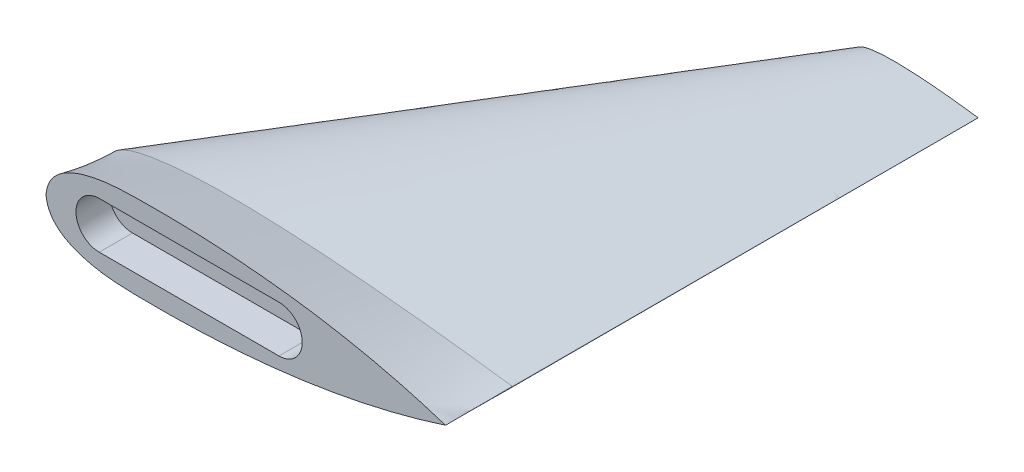
SolidWorks part; units mm, degrees
material "Nylon 101"
ref_plane "Front Plane" through (0, 0, 0) normal (0, 0, 1) x (1, 0, 0)
ref_plane "Top Plane" through (0, 0, 0) normal (0, 1, 0) x (1, 0, 0)
ref_plane "Right Plane" through (0, 0, 0) normal (1, 0, 0) x (0, 0, -1)
curve "Curve1"
  spline degree 3 poles (0.0247, -0.2632, 0) (-0.0121, 0, 0) (0.0247, 0.2632, 0) (0.1356, 0.5197, 0) (0.3168, 0.7666, 0) (0.5661, 1.0049, 0) (0.8827, 1.2355, 0) (1.2661, 1.4585, 0) (1.7158, 1.6738, 0) (2.231, 1.8809, 0) (2.8107, 2.0791, 0) (3.4535, 2.2677, 0) (4.1582, 2.4461, 0) (4.9231, 2.6137, 0) (5.7465, 2.7696, 0) (6.6264, 2.9134, 0) (7.5609, 3.0445, 0) (8.5477, 3.1624, 0) (9.5846, 3.2667, 0) (10.6691, 3.3571, 0) (11.7988, 3.4335, 0) (12.971, 3.4956, 0) (14.1829, 3.5434, 0) (15.4317, 3.5772, 0) (16.7145, 3.597, 0) (18.0284, 3.6032, 0) (19.3702, 3.5962, 0) (20.7368, 3.5763, 0) (22.1251, 3.5442, 0) (23.5317, 3.5004, 0) (24.9534, 3.4457, 0) (26.3869, 3.3806, 0) (27.8289, 3.3059, 0) (29.2759, 3.2225, 0) (30.7246, 3.131, 0) (32.1716, 3.0322, 0) (33.6135, 2.927, 0) (35.047, 2.816, 0) (36.4687, 2.7001, 0) (37.8753, 2.58, 0) (39.2635, 2.4565, 0) (40.6301, 2.3301, 0) (41.9718, 2.2018, 0) (43.2856, 2.072, 0) (44.5683, 1.9415, 0) (45.8171, 1.8109, 0) (47.0288, 1.6809, 0) (48.2009, 1.5521, 0) (49.3304, 1.425, 0) (50.4147, 1.3003, 0) (51.4514, 1.1787, 0) (52.438, 1.0606, 0) (53.3721, 0.9467, 0) (54.2517, 0.8375, 0) (55.0747, 0.7337, 0) (55.839, 0.6357, 0) (56.5431, 0.5442, 0) (57.1851, 0.4596, 0) (57.7637, 0.3825, 0) (58.2774, 0.3132, 0) (58.7251, 0.2523, 0) (59.1055, 0.1998, 0) (59.4184, 0.1573, 0) (59.6615, 0.1216, 0) (59.8381, 0.1013, 0) (59.9395, 0.0794, 0) (60.0436, 0.0813, 0) (60.0436, -0.0813, 0) (59.9395, -0.0794, 0) (59.8381, -0.1013, 0) (59.6615, -0.1216, 0) (59.4184, -0.1573, 0) (59.1055, -0.1998, 0) (58.7251, -0.2523, 0) (58.2774, -0.3132, 0) (57.7637, -0.3825, 0) (57.1851, -0.4596, 0) (56.5431, -0.5442, 0) (55.839, -0.6357, 0) (55.0747, -0.7337, 0) (54.2517, -0.8375, 0) (53.3721, -0.9467, 0) (52.438, -1.0606, 0) (51.4514, -1.1787, 0) (50.4147, -1.3003, 0) (49.3304, -1.425, 0) (48.2009, -1.5521, 0) (47.0288, -1.6809, 0) (45.8171, -1.8109, 0) (44.5683, -1.9415, 0) (43.2856, -2.072, 0) (41.9718, -2.2018, 0) (40.6301, -2.3301, 0) (39.2635, -2.4565, 0) (37.8753, -2.58, 0) (36.4687, -2.7001, 0) (35.047, -2.816, 0) (33.6135, -2.927, 0) (32.1716, -3.0322, 0) (30.7246, -3.131, 0) (29.2759, -3.2225, 0) (27.8289, -3.3059, 0) (26.3869, -3.3806, 0) (24.9534, -3.4457, 0) (23.5317, -3.5004, 0) (22.1251, -3.5442, 0) (20.7368, -3.5763, 0) (19.3702, -3.5962, 0) (18.0284, -3.6032, 0) (16.7145, -3.597, 0) (15.4317, -3.5772, 0) (14.1829, -3.5434, 0) (12.971, -3.4956, 0) (11.7988, -3.4335, 0) (10.6691, -3.3571, 0) (9.5846, -3.2667, 0) (8.5477, -3.1624, 0) (7.5609, -3.0445, 0) (6.6264, -2.9134, 0) (5.7465, -2.7696, 0) (4.9231, -2.6137, 0) (4.1582, -2.4461, 0) (3.4535, -2.2677, 0) (2.8107, -2.0791, 0) (2.231, -1.8809, 0) (1.7158, -1.6738, 0) (1.2661, -1.4585, 0) (0.8827, -1.2355, 0) (0.5661, -1.0049, 0) (0.3168, -0.7666, 0) (0.1356, -0.5197, 0) (0.0247, -0.2632, 0) (-0.0121, 0, 0) (0.0247, 0.2632, 0) knots -0.006773 -0.004321 -0.002106 0 0.002106 0.004321 0.006773 0.009557 0.012734 0.016343 0.020406 0.024934 0.029933 0.035402 0.041337 0.047732 0.054575 0.061857 0.069565 0.077682 0.086195 0.095084 0.104333 0.113922 0.123829 0.134035 0.144516 0.155249 0.16621 0.177376 0.18872 0.200217 0.21184 0.223563 0.235359 0.2472 0.259058 0.270907 0.282718 0.294465 0.306118 0.317651 0.329037 0.340249 0.35126 0.362045 0.372579 0.382836 0.392793 0.402425 0.411711 0.420628 0.429156 0.437273 0.444962 0.452203 0.458979 0.465275 0.471075 0.476366 0.481134 0.485369 0.48906 0.492198 0.494776 0.496788 0.498228 0.499094 0.499383 0.500617 0.500906 0.501772 0.503212 0.505224 0.507802 0.51094 0.514631 0.518866 0.523634 0.528925 0.534725 0.541021 0.547797 0.555038 0.562727 0.570844 0.579372 0.588289 0.597575 0.607207 0.617164 0.627421 0.637955 0.64874 0.659751 0.670963 0.682349 0.693882 0.705535 0.717282 0.729093 0.740942 0.7528 0.764641 0.776437 0.78816 0.799783 0.81128 0.822624 0.83379 0.844751 0.855484 0.865965 0.876171 0.886078 0.895667 0.904916 0.913805 0.922318 0.930435 0.938143 0.945425 0.952268 0.958663 0.964598 0.970067 0.975066 0.979594 0.983657 0.987266 0.990443 0.993227 0.995679 0.997894 1 1.002106 1.004321 1.006773 periodic
sketch "Sketch2" plane through (0, 0, 0) normal (0, 0, 1) x (1, 0, 0)
  spline S0 degree 3 poles (0.0247, 0.2632) (-0.0121, 0) (0.0247, -0.2632) (0.1356, -0.5197) (0.3168, -0.7666) (0.5661, -1.0049) (0.8827, -1.2355) (1.2661, -1.4585) (1.7158, -1.6738) (2.231, -1.8809) (2.8107, -2.0791) (3.4535, -2.2677) (4.1582, -2.4461) (4.9231, -2.6137) (5.7465, -2.7696) (6.6264, -2.9134) (7.5609, -3.0445) (8.5477, -3.1624) (9.5846, -3.2667) (10.6691, -3.3571) (11.7988, -3.4335) (12.971, -3.4956) (14.1829, -3.5434) (15.4317, -3.5772) (16.7145, -3.597) (18.0284, -3.6032) (19.3702, -3.5962) (20.7368, -3.5763) (22.1251, -3.5442) (23.5317, -3.5004) (24.9534, -3.4457) (26.3869, -3.3806) (27.8289, -3.3059) (29.2759, -3.2225) (30.7246, -3.131) (32.1716, -3.0322) (33.6135, -2.927) (35.047, -2.816) (36.4687, -2.7001) (37.8753, -2.58) (39.2635, -2.4565) (40.6301, -2.3301) (41.9718, -2.2018) (43.2856, -2.072) (44.5683, -1.9415) (45.8171, -1.8109) (47.0288, -1.6809) (48.2009, -1.5521) (49.3304, -1.425) (50.4147, -1.3003) (51.4514, -1.1787) (52.438, -1.0606) (53.3721, -0.9467) (54.2517, -0.8375) (55.0747, -0.7337) (55.839, -0.6357) (56.5431, -0.5442) (57.1851, -0.4596) (57.7637, -0.3825) (58.2774, -0.3132) (58.7251, -0.2523) (59.1055, -0.1998) (59.4184, -0.1573) (59.6615, -0.1216) (59.8381, -0.1013) (59.9395, -0.0794) (60.0436, -0.0813) (60.0436, 0.0813) (59.9395, 0.0794) (59.8381, 0.1013) (59.6615, 0.1216) (59.4184, 0.1573) (59.1055, 0.1998) (58.7251, 0.2523) (58.2774, 0.3132) (57.7637, 0.3825) (57.1851, 0.4596) (56.5431, 0.5442) (55.839, 0.6357) (55.0747, 0.7337) (54.2517, 0.8375) (53.3721, 0.9467) (52.438, 1.0606) (51.4514, 1.1787) (50.4147, 1.3003) (49.3304, 1.425) (48.2009, 1.5521) (47.0288, 1.6809) (45.8171, 1.8109) (44.5683, 1.9415) (43.2856, 2.072) (41.9718, 2.2018) (40.6301, 2.3301) (39.2635, 2.4565) (37.8753, 2.58) (36.4687, 2.7001) (35.047, 2.816) (33.6135, 2.927) (32.1716, 3.0322) (30.7246, 3.131) (29.2759, 3.2225) (27.8289, 3.3059) (26.3869, 3.3806) (24.9534, 3.4457) (23.5317, 3.5004) (22.1251, 3.5442) (20.7368, 3.5763) (19.3702, 3.5962) (18.0284, 3.6032) (16.7145, 3.597) (15.4317, 3.5772) (14.1829, 3.5434) (12.971, 3.4956) (11.7988, 3.4335) (10.6691, 3.3571) (9.5846, 3.2667) (8.5477, 3.1624) (7.5609, 3.0445) (6.6264, 2.9134) (5.7465, 2.7696) (4.9231, 2.6137) (4.1582, 2.4461) (3.4535, 2.2677) (2.8107, 2.0791) (2.231, 1.8809) (1.7158, 1.6738) (1.2661, 1.4585) (0.8827, 1.2355) (0.5661, 1.0049) (0.3168, 0.7666) (0.1356, 0.5197) (0.0247, 0.2632) (-0.0121, 0) (0.0247, -0.2632) knots -0.006773 -0.004321 -0.002106 0 0.002106 0.004321 0.006773 0.009557 0.012734 0.016343 0.020406 0.024934 0.029933 0.035402 0.041337 0.047732 0.054575 0.061857 0.069565 0.077682 0.086195 0.095084 0.104333 0.113922 0.123829 0.134035 0.144516 0.155249 0.16621 0.177376 0.18872 0.200217 0.21184 0.223563 0.235359 0.2472 0.259058 0.270907 0.282718 0.294465 0.306118 0.317651 0.329037 0.340249 0.35126 0.362045 0.372579 0.382836 0.392793 0.402425 0.411711 0.420628 0.429156 0.437273 0.444962 0.452203 0.458979 0.465275 0.471075 0.476366 0.481134 0.485369 0.48906 0.492198 0.494776 0.496788 0.498228 0.499094 0.499383 0.500617 0.500906 0.501772 0.503212 0.505224 0.507802 0.51094 0.514631 0.518866 0.523634 0.528925 0.534725 0.541021 0.547797 0.555038 0.562727 0.570844 0.579372 0.588289 0.597575 0.607207 0.617164 0.627421 0.637955 0.64874 0.659751 0.670963 0.682349 0.693882 0.705535 0.717282 0.729093 0.740942 0.7528 0.764641 0.776437 0.78816 0.799783 0.81128 0.822624 0.83379 0.844751 0.855484 0.865965 0.876171 0.886078 0.895667 0.904916 0.913805 0.922318 0.930435 0.938143 0.945425 0.952268 0.958663 0.964598 0.970067 0.975066 0.979594 0.983657 0.987266 0.990443 0.993227 0.995679 0.997894 1 1.002106 1.004321 1.006773 only from (0, 0) to (0, 0) construction
  spline S1 degree 3 poles (0.0247, 0.2632) (-0.0121, 0) (0.0247, -0.2632) (0.1356, -0.5197) (0.3168, -0.7666) (0.5661, -1.0049) (0.8827, -1.2355) (1.2661, -1.4585) (1.7158, -1.6738) (2.231, -1.8809) (2.8107, -2.0791) (3.4535, -2.2677) (4.1582, -2.4461) (4.9231, -2.6137) (5.7465, -2.7696) (6.6264, -2.9134) (7.5609, -3.0445) (8.5477, -3.1624) (9.5846, -3.2667) (10.6691, -3.3571) (11.7988, -3.4335) (12.971, -3.4956) (14.1829, -3.5434) (15.4317, -3.5772) (16.7145, -3.597) (18.0284, -3.6032) (19.3702, -3.5962) (20.7368, -3.5763) (22.1251, -3.5442) (23.5317, -3.5004) (24.9534, -3.4457) (26.3869, -3.3806) (27.8289, -3.3059) (29.2759, -3.2225) (30.7246, -3.131) (32.1716, -3.0322) (33.6135, -2.927) (35.047, -2.816) (36.4687, -2.7001) (37.8753, -2.58) (39.2635, -2.4565) (40.6301, -2.3301) (41.9718, -2.2018) (43.2856, -2.072) (44.5683, -1.9415) (45.8171, -1.8109) (47.0288, -1.6809) (48.2009, -1.5521) (49.3304, -1.425) (50.4147, -1.3003) (51.4514, -1.1787) (52.438, -1.0606) (53.3721, -0.9467) (54.2517, -0.8375) (55.0747, -0.7337) (55.839, -0.6357) (56.5431, -0.5442) (57.1851, -0.4596) (57.7637, -0.3825) (58.2774, -0.3132) (58.7251, -0.2523) (59.1055, -0.1998) (59.4184, -0.1573) (59.6615, -0.1216) (59.8381, -0.1013) (59.9395, -0.0794) (60.0436, -0.0813) (60.0436, 0.0813) (59.9395, 0.0794) (59.8381, 0.1013) (59.6615, 0.1216) (59.4184, 0.1573) (59.1055, 0.1998) (58.7251, 0.2523) (58.2774, 0.3132) (57.7637, 0.3825) (57.1851, 0.4596) (56.5431, 0.5442) (55.839, 0.6357) (55.0747, 0.7337) (54.2517, 0.8375) (53.3721, 0.9467) (52.438, 1.0606) (51.4514, 1.1787) (50.4147, 1.3003) (49.3304, 1.425) (48.2009, 1.5521) (47.0288, 1.6809) (45.8171, 1.8109) (44.5683, 1.9415) (43.2856, 2.072) (41.9718, 2.2018) (40.6301, 2.3301) (39.2635, 2.4565) (37.8753, 2.58) (36.4687, 2.7001) (35.047, 2.816) (33.6135, 2.927) (32.1716, 3.0322) (30.7246, 3.131) (29.2759, 3.2225) (27.8289, 3.3059) (26.3869, 3.3806) (24.9534, 3.4457) (23.5317, 3.5004) (22.1251, 3.5442) (20.7368, 3.5763) (19.3702, 3.5962) (18.0284, 3.6032) (16.7145, 3.597) (15.4317, 3.5772) (14.1829, 3.5434) (12.971, 3.4956) (11.7988, 3.4335) (10.6691, 3.3571) (9.5846, 3.2667) (8.5477, 3.1624) (7.5609, 3.0445) (6.6264, 2.9134) (5.7465, 2.7696) (4.9231, 2.6137) (4.1582, 2.4461) (3.4535, 2.2677) (2.8107, 2.0791) (2.231, 1.8809) (1.7158, 1.6738) (1.2661, 1.4585) (0.8827, 1.2355) (0.5661, 1.0049) (0.3168, 0.7666) (0.1356, 0.5197) (0.0247, 0.2632) (-0.0121, 0) (0.0247, -0.2632) knots -0.006773 -0.004321 -0.002106 0 0.002106 0.004321 0.006773 0.009557 0.012734 0.016343 0.020406 0.024934 0.029933 0.035402 0.041337 0.047732 0.054575 0.061857 0.069565 0.077682 0.086195 0.095084 0.104333 0.113922 0.123829 0.134035 0.144516 0.155249 0.16621 0.177376 0.18872 0.200217 0.21184 0.223563 0.235359 0.2472 0.259058 0.270907 0.282718 0.294465 0.306118 0.317651 0.329037 0.340249 0.35126 0.362045 0.372579 0.382836 0.392793 0.402425 0.411711 0.420628 0.429156 0.437273 0.444962 0.452203 0.458979 0.465275 0.471075 0.476366 0.481134 0.485369 0.48906 0.492198 0.494776 0.496788 0.498228 0.499094 0.499383 0.500617 0.500906 0.501772 0.503212 0.505224 0.507802 0.51094 0.514631 0.518866 0.523634 0.528925 0.534725 0.541021 0.547797 0.555038 0.562727 0.570844 0.579372 0.588289 0.597575 0.607207 0.617164 0.627421 0.637955 0.64874 0.659751 0.670963 0.682349 0.693882 0.705535 0.717282 0.729093 0.740942 0.7528 0.764641 0.776437 0.78816 0.799783 0.81128 0.822624 0.83379 0.844751 0.855484 0.865965 0.876171 0.886078 0.895667 0.904916 0.913805 0.922318 0.930435 0.938143 0.945425 0.952268 0.958663 0.964598 0.970067 0.975066 0.979594 0.983657 0.987266 0.990443 0.993227 0.995679 0.997894 1 1.002106 1.004321 1.006773 only from (0, 0) to (0, 0)
ref_plane "Plane1" through (0, 0, 70) normal (0, 0, 1) x (1, 0, 0)
sketch "Sketch3" plane through (0, 0, 70) normal (0, 0, 1) x (1, 0, 0)
  spline S1 degree 3 poles (42.0303, 0.079) (42.0193, 0) (42.0303, -0.079) (42.0636, -0.1559) (42.1179, -0.23) (42.1927, -0.3015) (42.2877, -0.3706) (42.4027, -0.4376) (42.5376, -0.5021) (42.6922, -0.5643) (42.8661, -0.6237) (43.0589, -0.6803) (43.2703, -0.7338) (43.4998, -0.7841) (43.7468, -0.8309) (44.0108, -0.874) (44.2911, -0.9134) (44.5872, -0.9487) (44.8983, -0.98) (45.2236, -1.0071) (45.5625, -1.03) (45.9142, -1.0487) (46.2777, -1.063) (46.6524, -1.0732) (47.0372, -1.0791) (47.4314, -1.081) (47.8339, -1.0789) (48.2439, -1.0729) (48.6604, -1.0633) (49.0824, -1.0501) (49.5089, -1.0337) (49.939, -1.0142) (50.3715, -0.9918) (50.8056, -0.9667) (51.2403, -0.9393) (51.6744, -0.9097) (52.1069, -0.8781) (52.537, -0.8448) (52.9635, -0.81) (53.3855, -0.774) (53.8019, -0.7369) (54.2119, -0.699) (54.6144, -0.6605) (55.0086, -0.6216) (55.3934, -0.5825) (55.768, -0.5433) (56.1315, -0.5043) (56.4831, -0.4656) (56.822, -0.4275) (57.1473, -0.3901) (57.4583, -0.3536) (57.7543, -0.3182) (58.0345, -0.284) (58.2984, -0.2513) (58.5453, -0.2201) (58.7746, -0.1907) (58.9858, -0.1633) (59.1784, -0.1379) (59.352, -0.1147) (59.5061, -0.094) (59.6404, -0.0757) (59.7545, -0.0599) (59.8484, -0.0472) (59.9213, -0.0365) (59.9743, -0.0304) (60.0047, -0.0238) (60.0359, -0.0244) (60.0359, 0.0244) (60.0047, 0.0238) (59.9743, 0.0304) (59.9213, 0.0365) (59.8484, 0.0472) (59.7545, 0.0599) (59.6404, 0.0757) (59.5061, 0.094) (59.352, 0.1147) (59.1784, 0.1379) (58.9858, 0.1633) (58.7746, 0.1907) (58.5453, 0.2201) (58.2984, 0.2513) (58.0345, 0.284) (57.7543, 0.3182) (57.4583, 0.3536) (57.1473, 0.3901) (56.822, 0.4275) (56.4831, 0.4656) (56.1315, 0.5043) (55.768, 0.5433) (55.3934, 0.5825) (55.0086, 0.6216) (54.6144, 0.6605) (54.2119, 0.699) (53.8019, 0.7369) (53.3855, 0.774) (52.9635, 0.81) (52.537, 0.8448) (52.1069, 0.8781) (51.6744, 0.9097) (51.2403, 0.9393) (50.8056, 0.9667) (50.3715, 0.9918) (49.939, 1.0142) (49.5089, 1.0337) (49.0824, 1.0501) (48.6604, 1.0633) (48.2439, 1.0729) (47.8339, 1.0789) (47.4314, 1.081) (47.0372, 1.0791) (46.6524, 1.0732) (46.2777, 1.063) (45.9142, 1.0487) (45.5625, 1.03) (45.2236, 1.0071) (44.8983, 0.98) (44.5872, 0.9487) (44.2911, 0.9134) (44.0108, 0.874) (43.7468, 0.8309) (43.4998, 0.7841) (43.2703, 0.7338) (43.0589, 0.6803) (42.8661, 0.6237) (42.6922, 0.5643) (42.5376, 0.5021) (42.4027, 0.4376) (42.2877, 0.3706) (42.1927, 0.3015) (42.1179, 0.23) (42.0636, 0.1559) (42.0303, 0.079) (42.0193, 0) (42.0303, -0.079) knots -0.006773 -0.004321 -0.002106 0 0.002106 0.004321 0.006773 0.009557 0.012734 0.016343 0.020406 0.024934 0.029933 0.035402 0.041337 0.047732 0.054575 0.061857 0.069565 0.077682 0.086195 0.095084 0.104333 0.113922 0.123829 0.134035 0.144516 0.155249 0.16621 0.177376 0.18872 0.200217 0.21184 0.223563 0.235359 0.2472 0.259058 0.270907 0.282718 0.294465 0.306118 0.317651 0.329037 0.340249 0.35126 0.362045 0.372579 0.382836 0.392793 0.402425 0.411711 0.420628 0.429156 0.437273 0.444962 0.452203 0.458979 0.465275 0.471075 0.476366 0.481134 0.485369 0.48906 0.492198 0.494776 0.496788 0.498228 0.499094 0.499383 0.500617 0.500906 0.501772 0.503212 0.505224 0.507802 0.51094 0.514631 0.518866 0.523634 0.528925 0.534725 0.541021 0.547797 0.555038 0.562727 0.570844 0.579372 0.588289 0.597575 0.607207 0.617164 0.627421 0.637955 0.64874 0.659751 0.670963 0.682349 0.693882 0.705535 0.717282 0.729093 0.740942 0.7528 0.764641 0.776437 0.78816 0.799783 0.81128 0.822624 0.83379 0.844751 0.855484 0.865965 0.876171 0.886078 0.895667 0.904916 0.913805 0.922318 0.930435 0.938143 0.945425 0.952268 0.958663 0.964598 0.970067 0.975066 0.979594 0.983657 0.987266 0.990443 0.993227 0.995679 0.997894 1 1.002106 1.004321 1.006773 only from (42.0229, 0) to (42.0229, 0)
loft "Loft1" add profiles "Sketch3", "Sketch2" connector at (42.0229, 0, 70) connector at (0, 0, 0)
ref_plane "Plane2" through (0, 0, -10) normal (0, 0, -1) x (-1, 0, 0)
sketch "Sketch8" plane through (0, 0, -10) normal (0, 0, -1) x (-1, 0, 0)
  line L0 (-60.0327, 0) -> (0, 0) construction
  spline S0 degree 3 poles (-60.0327, 0) (-45.2292, 4.8224) (-26.6873, 6.8711) (-5.795, 6.0929) (-0.2693, 3.2539) (0, 0) knots 0 0 0 0 0.739004 0.864029 1 1 1 1
  spline S1 degree 3 poles (-0.0247, -0.2632) (0.0121, 0) (-0.0247, 0.2632) (-0.1356, 0.5197) (-0.3168, 0.7666) (-0.5661, 1.0049) (-0.8827, 1.2355) (-1.2661, 1.4585) (-1.7158, 1.6738) (-2.231, 1.8809) (-2.8107, 2.0791) (-3.4535, 2.2677) (-4.1582, 2.4461) (-4.9231, 2.6137) (-5.7465, 2.7696) (-6.6264, 2.9134) (-7.5609, 3.0445) (-8.5477, 3.1624) (-9.5846, 3.2667) (-10.6691, 3.3571) (-11.7988, 3.4335) (-12.971, 3.4956) (-14.1829, 3.5434) (-15.4317, 3.5772) (-16.7145, 3.597) (-18.0284, 3.6032) (-19.3702, 3.5962) (-20.7368, 3.5763) (-22.1251, 3.5442) (-23.5317, 3.5004) (-24.9534, 3.4457) (-26.3869, 3.3806) (-27.8289, 3.3059) (-29.2759, 3.2225) (-30.7246, 3.131) (-32.1716, 3.0322) (-33.6135, 2.927) (-35.047, 2.816) (-36.4687, 2.7001) (-37.8753, 2.58) (-39.2635, 2.4565) (-40.6301, 2.3301) (-41.9718, 2.2018) (-43.2856, 2.072) (-44.5683, 1.9415) (-45.8171, 1.8109) (-47.0288, 1.6809) (-48.2009, 1.5521) (-49.3304, 1.425) (-50.4147, 1.3003) (-51.4514, 1.1787) (-52.438, 1.0606) (-53.3721, 0.9467) (-54.2517, 0.8375) (-55.0747, 0.7337) (-55.839, 0.6357) (-56.5431, 0.5442) (-57.1851, 0.4596) (-57.7637, 0.3825) (-58.2774, 0.3132) (-58.7251, 0.2523) (-59.1055, 0.1998) (-59.4184, 0.1573) (-59.6615, 0.1216) (-59.8381, 0.1013) (-59.9395, 0.0794) (-60.0436, 0.0813) (-60.0436, -0.0813) (-59.9395, -0.0794) (-59.8381, -0.1013) (-59.6615, -0.1216) (-59.4184, -0.1573) (-59.1055, -0.1998) (-58.7251, -0.2523) (-58.2774, -0.3132) (-57.7637, -0.3825) (-57.1851, -0.4596) (-56.5431, -0.5442) (-55.839, -0.6357) (-55.0747, -0.7337) (-54.2517, -0.8375) (-53.3721, -0.9467) (-52.438, -1.0606) (-51.4514, -1.1787) (-50.4147, -1.3003) (-49.3304, -1.425) (-48.2009, -1.5521) (-47.0288, -1.6809) (-45.8171, -1.8109) (-44.5683, -1.9415) (-43.2856, -2.072) (-41.9718, -2.2018) (-40.6301, -2.3301) (-39.2635, -2.4565) (-37.8753, -2.58) (-36.4687, -2.7001) (-35.047, -2.816) (-33.6135, -2.927) (-32.1716, -3.0322) (-30.7246, -3.131) (-29.2759, -3.2225) (-27.8289, -3.3059) (-26.3869, -3.3806) (-24.9534, -3.4457) (-23.5317, -3.5004) (-22.1251, -3.5442) (-20.7368, -3.5763) (-19.3702, -3.5962) (-18.0284, -3.6032) (-16.7145, -3.597) (-15.4317, -3.5772) (-14.1829, -3.5434) (-12.971, -3.4956) (-11.7988, -3.4335) (-10.6691, -3.3571) (-9.5846, -3.2667) (-8.5477, -3.1624) (-7.5609, -3.0445) (-6.6264, -2.9134) (-5.7465, -2.7696) (-4.9231, -2.6137) (-4.1582, -2.4461) (-3.4535, -2.2677) (-2.8107, -2.0791) (-2.231, -1.8809) (-1.7158, -1.6738) (-1.2661, -1.4585) (-0.8827, -1.2355) (-0.5661, -1.0049) (-0.3168, -0.7666) (-0.1356, -0.5197) (-0.0247, -0.2632) (0.0121, 0) (-0.0247, 0.2632) knots -0.006773 -0.004321 -0.002106 0 0.002106 0.004321 0.006773 0.009557 0.012734 0.016343 0.020406 0.024934 0.029933 0.035402 0.041337 0.047732 0.054575 0.061857 0.069565 0.077682 0.086195 0.095084 0.104333 0.113922 0.123829 0.134035 0.144516 0.155249 0.16621 0.177376 0.18872 0.200217 0.21184 0.223563 0.235359 0.2472 0.259058 0.270907 0.282718 0.294465 0.306118 0.317651 0.329037 0.340249 0.35126 0.362045 0.372579 0.382836 0.392793 0.402425 0.411711 0.420628 0.429156 0.437273 0.444962 0.452203 0.458979 0.465275 0.471075 0.476366 0.481134 0.485369 0.48906 0.492198 0.494776 0.496788 0.498228 0.499094 0.499383 0.500617 0.500906 0.501772 0.503212 0.505224 0.507802 0.51094 0.514631 0.518866 0.523634 0.528925 0.534725 0.541021 0.547797 0.555038 0.562727 0.570844 0.579372 0.588289 0.597575 0.607207 0.617164 0.627421 0.637955 0.64874 0.659751 0.670963 0.682349 0.693882 0.705535 0.717282 0.729093 0.740942 0.7528 0.764641 0.776437 0.78816 0.799783 0.81128 0.822624 0.83379 0.844751 0.855484 0.865965 0.876171 0.886078 0.895667 0.904916 0.913805 0.922318 0.930435 0.938143 0.945425 0.952268 0.958663 0.964598 0.970067 0.975066 0.979594 0.983657 0.987266 0.990443 0.993227 0.995679 0.997894 1 1.002106 1.004321 1.006773 only from (0, 0) to (0, 0) construction
  spline S2 degree 3 poles (-60.0327, 0) (-45.2292, -4.8224) (-26.6873, -6.8711) (-5.795, -6.0929) (-0.2693, -3.2539) (0, 0) knots 0 0 0 0 0.739004 0.864029 1 1 1 1
loft "Loft2" add profiles "Sketch8", "Sketch2<3>" connector at (0, 0, -10) connector at (60.019, 0.0575, 0)
sketch "Sketch2<3>" plane through (0, 0, 0) normal (0, 0, 1) x (1, 0, 0) same geometry as "Sketch2"
sketch "Sketch9" plane through (0, 0, -10) normal (0, 0, -1) x (-1, 0, 0)
  line L0 (-35, 0) -> (-8, 0) construction
  line L1 (-35, 3.5) -> (-8, 3.5)
  line L2 (-35, -3.5) -> (-8, -3.5)
  arc A0 (-35, 3.5) -> (-35, -3.5) centre (-35, 0) ccw
  arc A1 (-8, -3.5) -> (-8, 3.5) centre (-8, 0) ccw
  point P3 (-21.5, 0)
  point P8 (-38.5, 0)
  point P9 (-4.5, 0)
  dimension "D2" = 3.5
  dimension "D1" = 34
  dimension "D3" = 8
extrude "Cut-Extrude1" cut sketch "Sketch9" against normal blind 5
mirror "Mirror1" about plane through (28.9738, -5.9064, -10) normal (0, 0, 1) of bodies 107 101
delete or keep bodies "Body-Delete/Keep 1" type delete bodies bodies 107
